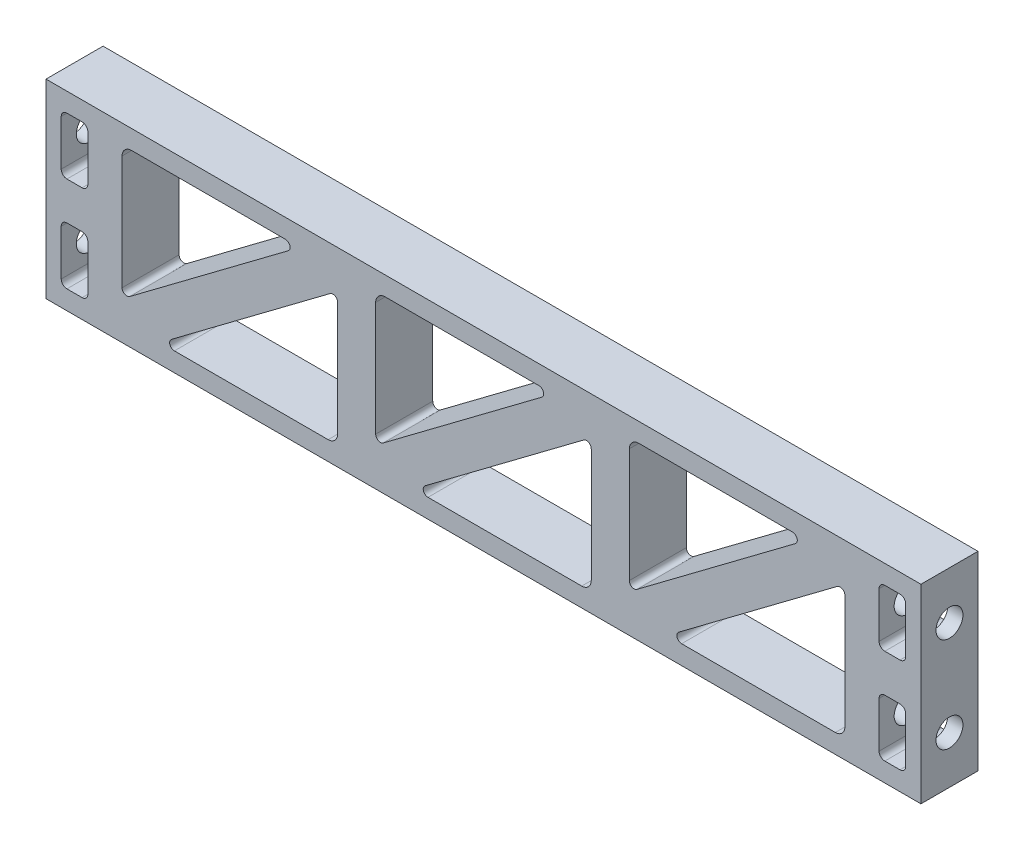
SolidWorks part; units mm, degrees
material "PE High Density"
ref_plane "Front Plane" through (0, 0, 0) normal (0, 0, 1) x (1, 0, 0)
ref_plane "Top Plane" through (0, 0, 0) normal (0, 1, 0) x (1, 0, 0)
ref_plane "Right Plane" through (0, 0, 0) normal (1, 0, 0) x (0, 0, -1)
sketch "Sketch1" plane through (0, 0, 0) normal (0, 0, 1) x (1, 0, 0)
  line L0 (-24.3417, 15.875) -> (-24.3417, -15.875) construction
  line L1 (-73.025, 15.875) -> (73.025, 15.875)
  line L2 (-73.025, 15.875) -> (-73.025, -15.875)
  line L3 (-73.025, -15.875) -> (73.025, -15.875)
  line L4 (73.025, 15.875) -> (73.025, -15.875)
  line L5 (-73.025, 15.875) -> (73.025, -15.875) construction
  line L6 (-73.025, -15.875) -> (73.025, 15.875) construction
  line L7 (24.3417, 15.875) -> (24.3417, -15.875) construction
  line L9 (-69.85, -12.7) -> (-27.5167, 12.7) construction
  line L10 (-69.85, -12.7) -> (-69.85, 12.7) construction
  line L11 (-64.3071, -11.2256) -> (-29.9209, 9.4061)
  line L12 (-73.025, -15.875) -> (-24.3417, -15.875)
  line L13 (-73.025, -15.875) -> (-73.025, 15.875)
  line L14 (-73.025, 15.875) -> (-24.3417, 15.875)
  line L15 (-24.3417, -15.875) -> (-24.3417, 15.875) construction
  line L16 (-69.85, 12.7) -> (-27.5167, 12.7) construction
  line L17 (-27.5167, -12.7) -> (-27.5167, 12.7) construction
  line L18 (-69.85, -12.7) -> (-27.5167, -12.7) construction
  line L19 (-67.4457, -9.4061) -> (-33.0595, 11.2256)
  line L20 (-69.0332, -14.0613) -> (-26.6999, 11.3387) construction
  line L21 (-69.85, -8.0448) -> (-69.85, 11.1125)
  line L22 (-70.6668, -11.3387) -> (-28.3334, 14.0613) construction
  line L23 (-68.2625, 12.7) -> (-33.4679, 12.7)
  line L24 (-63.8988, -12.7) -> (-29.1042, -12.7)
  line L25 (-27.5167, -11.1125) -> (-27.5167, 8.0448)
  line L26 (-15.6238, -11.2256) -> (18.7624, 9.4061)
  line L27 (-18.7624, -9.4061) -> (15.6238, 11.2256)
  line L28 (-21.1667, -8.0448) -> (-21.1667, 11.1125)
  line L29 (-19.5792, 12.7) -> (15.2154, 12.7)
  line L30 (-15.2154, -12.7) -> (19.5792, -12.7)
  line L31 (21.1667, -11.1125) -> (21.1667, 8.0448)
  line L32 (-21.1667, -12.7) -> (21.1667, 12.7) construction
  line L33 (-21.1667, -12.7) -> (-21.1667, 12.7) construction
  line L34 (-21.1667, 12.7) -> (21.1667, 12.7) construction
  line L35 (21.1667, -12.7) -> (21.1667, 12.7) construction
  line L36 (-21.1667, -12.7) -> (21.1667, -12.7) construction
  line L37 (33.0595, -11.2256) -> (67.4457, 9.4061)
  line L38 (29.9209, -9.4061) -> (64.3071, 11.2256)
  line L39 (27.5167, -8.0448) -> (27.5167, 11.1125)
  line L40 (29.1042, 12.7) -> (63.8988, 12.7)
  line L41 (33.4679, -12.7) -> (68.2625, -12.7)
  line L42 (69.85, -11.1125) -> (69.85, 8.0448)
  line L43 (27.5167, -12.7) -> (69.85, 12.7) construction
  line L44 (27.5167, -12.7) -> (27.5167, 12.7) construction
  line L45 (27.5167, 12.7) -> (69.85, 12.7) construction
  line L46 (69.85, -12.7) -> (69.85, 12.7) construction
  line L47 (27.5167, -12.7) -> (69.85, -12.7) construction
  line L59 (-64.3071, -11.2256) -> (-15.6238, -11.2256) construction
  line L60 (-69.85, 15.875) -> (-69.85, -15.875)
  arc A0 (-33.4679, 12.7) -> (-33.0595, 11.2256) centre (-33.4679, 11.9062) cw
  arc A1 (-69.85, -8.0448) -> (-67.4457, -9.4061) centre (-68.2625, -8.0448) ccw
  arc A2 (-69.85, 11.1125) -> (-68.2625, 12.7) centre (-68.2625, 11.1125) cw
  arc A3 (-27.5167, 8.0448) -> (-29.9209, 9.4061) centre (-29.1042, 8.0448) ccw
  arc A4 (-63.8988, -12.7) -> (-64.3071, -11.2256) centre (-63.8988, -11.9062) cw
  arc A5 (-27.5167, -11.1125) -> (-29.1042, -12.7) centre (-29.1042, -11.1125) cw
  arc A6 (15.2154, 12.7) -> (15.6238, 11.2256) centre (15.2154, 11.9062) cw
  arc A7 (-21.1667, -8.0448) -> (-18.7624, -9.4061) centre (-19.5792, -8.0448) ccw
  arc A8 (-21.1667, 11.1125) -> (-19.5792, 12.7) centre (-19.5792, 11.1125) cw
  arc A9 (21.1667, 8.0448) -> (18.7624, 9.4061) centre (19.5792, 8.0448) ccw
  arc A10 (-15.2154, -12.7) -> (-15.6238, -11.2256) centre (-15.2154, -11.9062) cw
  arc A11 (21.1667, -11.1125) -> (19.5792, -12.7) centre (19.5792, -11.1125) cw
  arc A12 (63.8988, 12.7) -> (64.3071, 11.2256) centre (63.8988, 11.9062) cw
  arc A13 (27.5167, -8.0448) -> (29.9209, -9.4061) centre (29.1042, -8.0448) ccw
  arc A14 (27.5167, 11.1125) -> (29.1042, 12.7) centre (29.1042, 11.1125) cw
  arc A15 (69.85, 8.0448) -> (67.4457, 9.4061) centre (68.2625, 8.0448) ccw
  arc A16 (33.4679, -12.7) -> (33.0595, -11.2256) centre (33.4679, -11.9062) cw
  arc A17 (69.85, -11.1125) -> (68.2625, -12.7) centre (68.2625, -11.1125) cw
  point P0 (0, 0)
  point P26 (-30.6022, 12.7)
  point P29 (-69.85, -10.8487)
  point P35 (-27.5167, 10.8487)
  point P38 (-66.7645, -12.7)
  dimension "D7" = 0.7937
  dimension "D8" = 1.5875
  dimension "D9" = 1.5875
  dimension "D10" = 1.5875
  dimension "D11" = 0.7937
  dimension "D12" = 1.5875
  dimension "D1" = 31.75
  dimension "CrossBraceLength" = 146.05
  dimension "D4" = 48.6833
  dimension "D14" = 48.6833
  dimension "D6" = 3.175
  dimension "D2" = 1.5875
  dimension "D5" = 1.5875
  dimension "D3" = 3
  dimension "D13" = 3
extrude "Boss-Extrude1" [suppressed] add sketch "Sketch1" along normal blind 9.525
sketch "Sketch2" plane through (0, 0, 0) normal (0, 0, 1) x (1, 0, 0)
  line L0 (-63.5, 15.875) -> (-63.5, -15.875) construction
  line L1 (-73.025, 15.875) -> (73.025, 15.875)
  line L2 (-73.025, 15.875) -> (-73.025, -15.875)
  line L3 (-73.025, -15.875) -> (73.025, -15.875)
  line L4 (73.025, 15.875) -> (73.025, -15.875)
  line L5 (-73.025, 15.875) -> (73.025, -15.875) construction
  line L6 (-73.025, -15.875) -> (73.025, 15.875) construction
  line L7 (63.5, 15.875) -> (63.5, -15.875) construction
  line L8 (-63.5, -15.875) -> (-63.5, 15.875) construction
  line L9 (-21.1667, -15.875) -> (-21.1667, 15.875) construction
  line L10 (21.1667, -15.875) -> (21.1667, 15.875) construction
  line L11 (-73.025, 0) -> (73.025, 0) construction
  line L12 (-63.5, -15.875) -> (-21.1667, -15.875) construction
  line L13 (-63.5, -15.875) -> (-21.1667, 15.875) construction
  line L14 (-63.5, -15.875) -> (-63.5, 15.875) construction
  line L15 (-63.5, 15.875) -> (-21.1667, 15.875)
  line L16 (-58.7375, 12.7) -> (-33.0729, 12.7)
  line L17 (-59.055, -8.5725) -> (-32.5967, 11.2713)
  line L18 (-60.325, -7.9375) -> (-60.325, 11.1125)
  line L19 (-60.325, 12.7) -> (-30.6917, 12.7) construction
  line L20 (-60.325, -9.525) -> (-30.6917, 12.7) construction
  line L21 (-60.325, -9.525) -> (-60.325, 12.7) construction
  line L22 (-63.5, -15.875) -> (-21.1667, -15.875)
  line L23 (-21.1667, -15.875) -> (-21.1667, 15.875) construction
  line L24 (-51.5938, -12.7) -> (-25.9292, -12.7)
  line L25 (-24.3417, -11.1125) -> (-24.3417, 7.9375)
  line L26 (-52.07, -11.2713) -> (-25.6117, 8.5725)
  line L27 (-53.975, -12.7) -> (-24.3417, 9.525) construction
  line L28 (-24.3417, -12.7) -> (-24.3417, 9.525) construction
  line L29 (-53.975, -12.7) -> (-24.3417, -12.7) construction
  line L30 (17.9917, -11.1125) -> (17.9917, 7.9375)
  line L31 (-9.2604, -12.7) -> (16.4042, -12.7)
  line L32 (-9.7367, -11.2713) -> (16.7217, 8.5725)
  line L33 (-16.7217, -8.5725) -> (9.7367, 11.2713)
  line L34 (-16.4042, 12.7) -> (9.2604, 12.7)
  line L35 (-17.9917, -7.9375) -> (-17.9917, 11.1125)
  line L36 (60.325, -11.1125) -> (60.325, 7.9375)
  line L37 (33.0729, -12.7) -> (58.7375, -12.7)
  line L38 (32.5967, -11.2713) -> (59.055, 8.5725)
  line L39 (25.6117, -8.5725) -> (52.07, 11.2713)
  line L40 (25.9292, 12.7) -> (51.5937, 12.7)
  line L41 (24.3417, -7.9375) -> (24.3417, 11.1125)
  line L48 (-24.3417, -11.1125) -> (17.9917, -11.1125) construction
  line L61 (-69.5325, 12.7) -> (-66.9925, 12.7)
  line L62 (-70.485, 11.7475) -> (-70.485, 4.1275)
  line L63 (-69.5325, 3.175) -> (-66.9925, 3.175)
  line L64 (-66.04, 11.7475) -> (-66.04, 4.1275)
  line L65 (-70.485, 12.7) -> (-66.04, 3.175) construction
  line L66 (-70.485, 3.175) -> (-66.04, 12.7) construction
  line L67 (-68.2625, 15.875) -> (-68.2625, -15.875) construction
  line L68 (-68.2625, 3.175) -> (-68.2625, 11.967) construction
  line L69 (-70.485, 7.9375) -> (-66.04, 7.9375) construction
  line L70 (-70.485, -7.9375) -> (-66.04, -7.9375) construction
  line L71 (-68.2625, -3.175) -> (-68.2625, -11.967) construction
  line L72 (-70.485, -3.175) -> (-66.04, -12.7) construction
  line L73 (-70.485, -12.7) -> (-66.04, -3.175) construction
  line L74 (-66.04, -11.7475) -> (-66.04, -4.1275)
  line L75 (-69.5325, -3.175) -> (-66.9925, -3.175)
  line L76 (-70.485, -11.7475) -> (-70.485, -4.1275)
  line L77 (-69.5325, -12.7) -> (-66.9925, -12.7)
  line L78 (0, -15.875) -> (0, 15.875) construction
  line L79 (70.485, -12.7) -> (66.04, -3.175) construction
  line L80 (70.485, -3.175) -> (66.04, -12.7) construction
  line L81 (68.2625, -3.175) -> (68.2625, -11.967) construction
  line L82 (70.485, -7.9375) -> (66.04, -7.9375) construction
  line L83 (70.485, 7.9375) -> (66.04, 7.9375) construction
  line L84 (68.2625, 3.175) -> (68.2625, 11.967) construction
  line L85 (68.2625, 15.875) -> (68.2625, -15.875) construction
  line L86 (70.485, 3.175) -> (66.04, 12.7) construction
  line L87 (70.485, 12.7) -> (66.04, 3.175) construction
  line L88 (69.5325, -12.7) -> (66.9925, -12.7)
  line L89 (70.485, -11.7475) -> (70.485, -4.1275)
  line L90 (69.5325, -3.175) -> (66.9925, -3.175)
  line L91 (66.04, -11.7475) -> (66.04, -4.1275)
  line L92 (66.04, 11.7475) -> (66.04, 4.1275)
  line L93 (69.5325, 3.175) -> (66.9925, 3.175)
  line L94 (70.485, 11.7475) -> (70.485, 4.1275)
  line L95 (69.5325, 12.7) -> (66.9925, 12.7)
  line L96 (73.025, 15.875) -> (73.025, -15.875)
  arc A0 (-33.0729, 12.7) -> (-32.5967, 11.2713) centre (-33.0729, 11.9063) cw
  arc A1 (-60.325, 11.1125) -> (-58.7375, 12.7) centre (-58.7375, 11.1125) cw
  arc A2 (-60.325, -7.9375) -> (-59.055, -8.5725) centre (-59.5313, -7.9375) ccw
  arc A3 (-25.6117, 8.5725) -> (-24.3417, 7.9375) centre (-25.1354, 7.9375) cw
  arc A4 (-25.9292, -12.7) -> (-24.3417, -11.1125) centre (-25.9292, -11.1125) ccw
  arc A5 (-51.5938, -12.7) -> (-52.07, -11.2713) centre (-51.5938, -11.9063) cw
  arc A6 (16.4042, -12.7) -> (17.9917, -11.1125) centre (16.4042, -11.1125) ccw
  arc A7 (-9.2604, -12.7) -> (-9.7367, -11.2713) centre (-9.2604, -11.9063) cw
  arc A8 (16.7217, 8.5725) -> (17.9917, 7.9375) centre (17.1979, 7.9375) cw
  arc A9 (9.2604, 12.7) -> (9.7367, 11.2713) centre (9.2604, 11.9063) cw
  arc A10 (-17.9917, 11.1125) -> (-16.4042, 12.7) centre (-16.4042, 11.1125) cw
  arc A11 (-17.9917, -7.9375) -> (-16.7217, -8.5725) centre (-17.1979, -7.9375) ccw
  arc A12 (58.7375, -12.7) -> (60.325, -11.1125) centre (58.7375, -11.1125) ccw
  arc A13 (33.0729, -12.7) -> (32.5967, -11.2713) centre (33.0729, -11.9063) cw
  arc A14 (59.055, 8.5725) -> (60.325, 7.9375) centre (59.5312, 7.9375) cw
  arc A15 (51.5937, 12.7) -> (52.07, 11.2713) centre (51.5937, 11.9063) cw
  arc A16 (24.3417, 11.1125) -> (25.9292, 12.7) centre (25.9292, 11.1125) cw
  arc A17 (24.3417, -7.9375) -> (25.6117, -8.5725) centre (25.1354, -7.9375) ccw
  arc A36 (-66.9925, 3.175) -> (-66.04, 4.1275) centre (-66.9925, 4.1275) ccw
  arc A37 (-66.9925, 12.7) -> (-66.04, 11.7475) centre (-66.9925, 11.7475) cw
  arc A38 (-69.5325, 3.175) -> (-70.485, 4.1275) centre (-69.5325, 4.1275) cw
  arc A39 (-69.5325, 12.7) -> (-70.485, 11.7475) centre (-69.5325, 11.7475) ccw
  arc A40 (-69.5325, -12.7) -> (-70.485, -11.7475) centre (-69.5325, -11.7475) cw
  arc A41 (-69.5325, -3.175) -> (-70.485, -4.1275) centre (-69.5325, -4.1275) ccw
  arc A42 (-66.9925, -12.7) -> (-66.04, -11.7475) centre (-66.9925, -11.7475) ccw
  arc A43 (-66.9925, -3.175) -> (-66.04, -4.1275) centre (-66.9925, -4.1275) cw
  arc A44 (66.9925, -3.175) -> (66.04, -4.1275) centre (66.9925, -4.1275) ccw
  arc A45 (66.9925, -12.7) -> (66.04, -11.7475) centre (66.9925, -11.7475) cw
  arc A46 (69.5325, -3.175) -> (70.485, -4.1275) centre (69.5325, -4.1275) cw
  arc A47 (69.5325, -12.7) -> (70.485, -11.7475) centre (69.5325, -11.7475) ccw
  arc A48 (69.5325, 12.7) -> (70.485, 11.7475) centre (69.5325, 11.7475) cw
  arc A49 (69.5325, 3.175) -> (70.485, 4.1275) centre (69.5325, 4.1275) ccw
  arc A50 (66.9925, 12.7) -> (66.04, 11.7475) centre (66.9925, 11.7475) ccw
  arc A51 (66.9925, 3.175) -> (66.04, 4.1275) centre (66.9925, 4.1275) cw
  point P0 (0, 0)
  point P16 (-68.2625, 7.9375)
  point P124 (-68.2625, -7.9375)
  point P168 (68.2625, -7.9375)
  point P169 (68.2625, 7.9375)
  dimension "D9" = 1.5875
  dimension "D8" = 0.7937
  dimension "D10" = 0.7937
  dimension "D12" = 0.7937
  dimension "D13" = 1.5875
  dimension "D14" = 0.7937
  dimension "D19" = 0.9525
  dimension "D20" = 0.9525
  dimension "D21" = 0.9525
  dimension "D22" = 0.9525
  dimension "D1" = 146.05
  dimension "D2" = 31.75
  dimension "D3" = 9.525
  dimension "D4" = 9.525
  dimension "D6" = 42.3333
  dimension "D15" = 42.3333
  dimension "D17" = 4.445
  dimension "D18" = 9.525
  dimension "D23" = 4.7625
  dimension "D24" = 7.9375
  dimension "D7" = 3.175
  dimension "D11" = 3.175
  dimension "D5" = 3
  dimension "D16" = 3
extrude "Boss-Extrude2" add sketch "Sketch2" along normal blind 9.525 contours L4 L1 L2 L3 A17 L41 A16 L40 A15 L39 A11 L35 A10 L34 A9 L33 A2 L18 A1 L16 A0 L17 L24 A5 L26 A3 L25 A4 L32 A8 L30 A6 L31 A7 region at (0, 0, 0)
sketch "Sketch3" plane through (-73.025, 0, 0) normal (-1, 0, 0) x (0, 0, 1)
  line L0 (9.525, 15.875) -> (0, 15.875) construction
  line L1 (0, 0) -> (9.525, 0) construction
  line L2 (9.525, 15.875) -> (9.525, -15.875) construction
  line L3 (4.7625, -15.875) -> (4.7625, 15.875) construction
  line L4 (9.525, -15.875) -> (0, -15.875) construction
  circle A0 centre (4.7625, 7.9375) radius 2.2479
  dimension "D2" = 4.4958
  dimension "D1" = 7.9375
extrude "Cut-Extrude1" cut sketch "Sketch3" against normal blind 11.1125
mirror "Mirror1" about plane through (0, 0, 0) normal (1, 0, 0) of "Cut-Extrude1" second plane through (0, 0, 0) second plane normal (0, 1, 0)
equation "\"Plate Width\" = 4.6in"
equation "\"Plate Thickness\" = 0.375in"
equation "\"Num holes\" = 4"
equation "\"Plate Height\" = 1.25in"
equation "\"Top Plate Width\" = 4.5in"
equation "\"Plate Clearance Hole Diameter\" = 0.125in"
equation "\"Plate Tap Hole Diameter\" = 0.116in"
equation "\"Bottom Plate Length\" = 6.5in"
equation "\"CrossBraceLength@Sketch1\" = \"Bottom Plate Length\" - 2 * \"Plate Thickness\""
equation "\"D1@Sketch1\"=\"Plate Height\""
equation "\"num_triangle_holes\"= 3"
equation "\"D3@Sketch1\"=\"num_triangle_holes\""
equation "\"D4@Sketch1\"=( \"Bottom Plate Length\" - 2 * \"Plate Thickness\" ) / \"num_triangle_holes\""
equation "\"BorderThickness\"= 0.125"
equation "\"D6@Sketch1\"=\"BorderThickness\""
equation "\"D2@Sketch1\"=\"BorderThickness\"/2"
equation "\"D9@Sketch1\"=\"BorderThickness\"/2"
equation "\"D8@Sketch1\"=\"BorderThickness\"/2"
equation "\"D7@Sketch1\"=\"BorderThickness\"/4"
equation "\"D10@Sketch1\"=\"BorderThickness\"/2"
equation "\"D11@Sketch1\"=\"BorderThickness\"/4"
equation "\"D12@Sketch1\"=\"BorderThickness\"/2"
equation "\"D13@Sketch1\"=\"num_triangle_holes\""
equation "\"D14@Sketch1\"=( \"Bottom Plate Length\" - 2 * \"Plate Thickness\" ) / \"num_triangle_holes\""
equation "\"D1@Boss-Extrude1\"=\"Plate Thickness\""
equation "\"D1@Sketch2\"=\"Bottom Plate Length\" - 2 * \"Plate Thickness\""
equation "\"D2@Sketch2\"=\"Plate Height\""
equation "\"wall_thickness\"= 0.375"
equation "\"D3@Sketch2\"=\"wall_thickness\""
equation "\"D4@Sketch2\"=\"wall_thickness\""
equation "\"D5@Sketch2\"=\"num_triangle_holes\""
equation "\"D6@Sketch2\"=( \"Bottom Plate Length\" - 2 * \"Plate Thickness\" - 2 * \"wall_thickness\" ) / \"num_triangle_holes\" "
equation "\"D7@Sketch2\"=\"BorderThickness\""
equation "\"D8@Sketch2\"=\"BorderThickness\" / 4"
equation "\"D10@Sketch2\"=\"BorderThickness\" / 4"
equation "\"D11@Sketch2\"=\"BorderThickness\""
equation "\"D9@Sketch2\"=\"BorderThickness\"/2"
equation "\"D13@Sketch2\"=\"BorderThickness\"/2"
equation "\"D14@Sketch2\"=\"BorderThickness\"/4"
equation "\"D12@Sketch2\"=\"BorderThickness\"/4"
equation "\"D15@Sketch2\"=( \"Bottom Plate Length\" - 2 * \"Plate Thickness\" - 2 * \"wall_thickness\" ) / \"num_triangle_holes\""
equation "\"D1@Boss-Extrude2\"=\"Plate Thickness\""
equation "\"D16@Sketch2\"=\"num_triangle_holes\""
equation "\"D23@Sketch2\"=\"wall_thickness\"/2"
equation "\"D24@Sketch2\"=\"Plate Height\"/4"
equation "\"Number Eight Clearance Size\" = 0.177in"
equation "\"D1@Sketch3\"=\"Plate Height\" / 4"
equation "\"D2@Sketch3\"=\"Number Eight Clearance Size\""
equation "\"D1@Cut-Extrude1\"=(0.75 - \"Plate Thickness\") + 0.0625"
